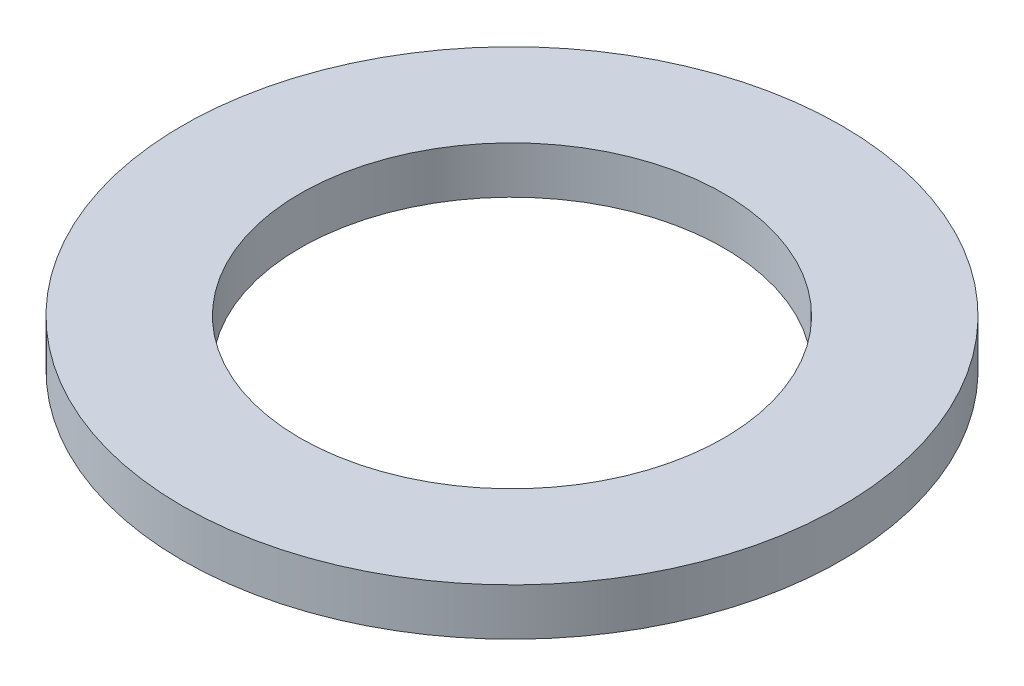
SolidWorks part; units mm, degrees
ref_plane "Front Plane" through (0, 0, 0) normal (0, 0, 1) x (1, 0, 0)
ref_plane "Top Plane" through (0, 0, 0) normal (0, 1, 0) x (1, 0, 0)
ref_plane "Right Plane" through (0, 0, 0) normal (1, 0, 0) x (0, 0, -1)
sketch "Sketch1" plane through (0, 0, 0) normal (0, 1, 0) x (1, 0, 0)
  circle A0 centre (0, 0) radius 70
  dimension "FLANGE_OD" = 140
extrude "Boss-Extrude1" add sketch "Sketch1" along normal blind 10
sketch "Sketch2" plane through (0, 0, 0) normal (0, 1, 0) x (1, 0, 0)
  circle A0 centre (0, 0) radius 45
  dimension "BORE_D" = 90
extrude "Cut-Extrude1" cut sketch "Sketch2" along normal through all
sketch "Sketch3" plane through (0, 10, 0) normal (0, 1, 0) x (1, 0, 0)
  circle A0 centre (0, 0) radius 28.1567 construction
  circle A1 centre (-28.1567, 0) radius 2.5629
  dimension "BOLT_D" = 5.1259
  dimension "BOLT_PCD" = 56.3134
extrude "Cut-Extrude2" cut sketch "Sketch3" against normal blind 9.2015 rebuild error yes
pattern_circular "CirPattern1" count 5 over 360 rebuild error yes
